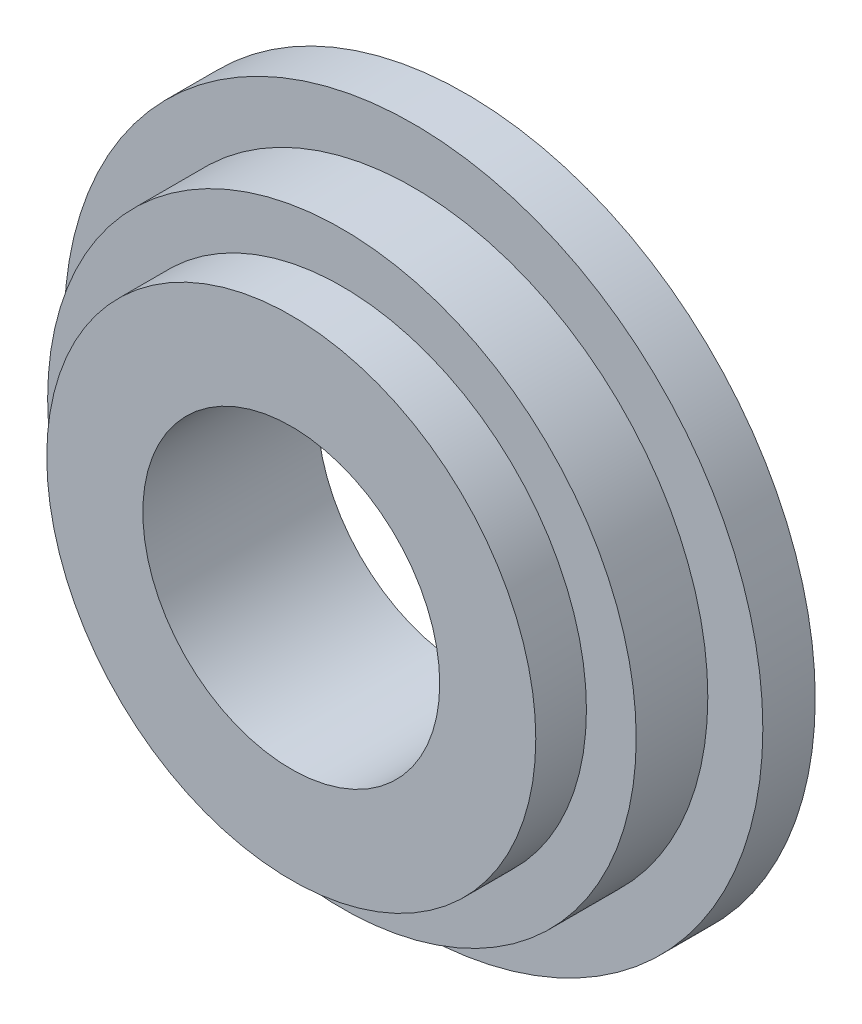
SolidWorks part; units mm, degrees
ref_plane "前视基准面" through (0, 0, 0) normal (0, 0, 1) x (1, 0, 0)
ref_plane "上视基准面" through (0, 0, 0) normal (0, 1, 0) x (1, 0, 0)
ref_plane "右视基准面" through (0, 0, 0) normal (1, 0, 0) x (0, 0, -1)
sketch "草图1" plane through (0, 0, 0) normal (0, 0, 1) x (1, 0, 0)
  circle A0 centre (0, 0) radius 8.5
  circle A1 centre (0, 0) radius 14
  circle A2 centre (0, 0) radius 16.85
  circle A3 centre (0, 0) radius 20
  dimension "D1" = 40
  dimension "D2" = 33.7
  dimension "D3" = 28
  dimension "D4" = 17
extrude "凸台-拉伸1" add sketch "草图1" along normal blind 3 contours A3 A2 region at (-19.4343, 0, 0)
extrude "凸台-拉伸2" add sketch "草图1<3>" along normal blind 7.1 contours A2 A1 region at (-16.3734, 0, 0)
sketch "草图1<3>" plane through (0, 0, 0) normal (0, 0, 1) x (1, 0, 0) same geometry as "草图1"
extrude "凸台-拉伸3" add sketch "草图1<4>" along normal blind 10 contours A1 A0 region at (-13.604, 0, 0)
sketch "草图1<4>" plane through (0, 0, 0) normal (0, 0, 1) x (1, 0, 0) same geometry as "草图1"
